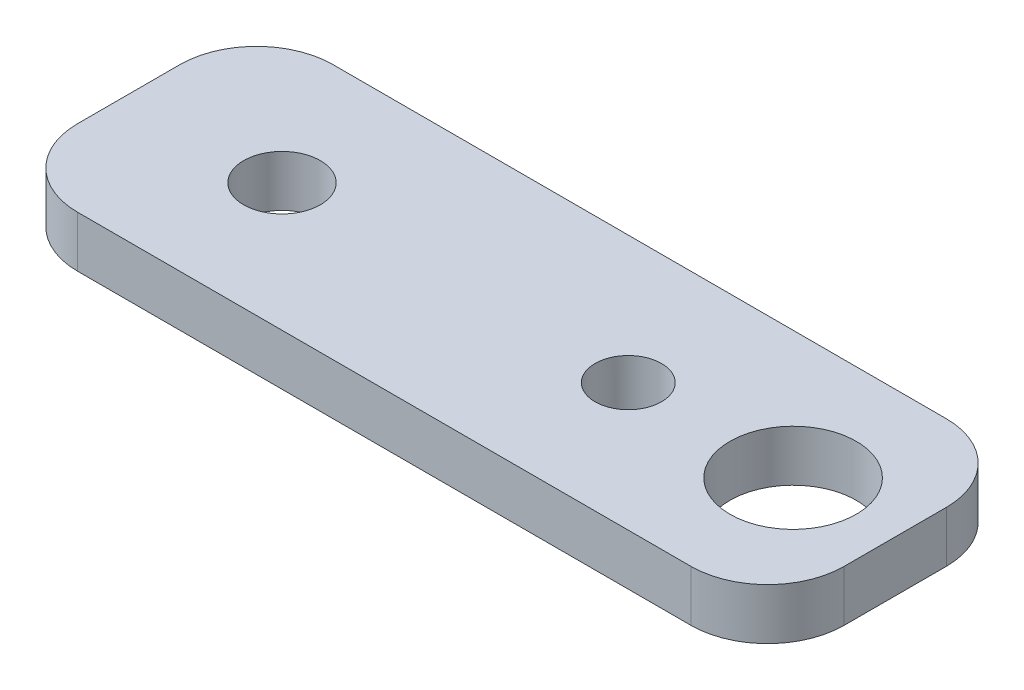
SolidWorks part; units mm, degrees
ref_plane "Front Plane" through (0, 0, 0) normal (0, 0, 1) x (1, 0, 0)
ref_plane "Top Plane" through (0, 0, 0) normal (0, 1, 0) x (1, 0, 0)
ref_plane "Right Plane" through (0, 0, 0) normal (1, 0, 0) x (0, 0, -1)
sketch "Sketch1" plane through (0, 0, 0) normal (0, 1, 0) x (1, 0, 0)
  line L1 (-15, 5) -> (15, 5)
  line L2 (-15, 5) -> (-15, -5)
  line L3 (-15, -5) -> (15, -5)
  line L4 (15, 5) -> (15, -5)
  line L5 (-15, 5) -> (15, -5) construction
  line L6 (-15, -5) -> (15, 5) construction
  point P0 (0, 0)
  dimension "D1" = 10
  dimension "D2" = 30
extrude "Boss-Extrude1" add sketch "Sketch1" along normal blind 2
sketch "Sketch2" plane through (0, 2, 0) normal (0, 1, 0) x (1, 0, 0)
  line L0 (11, 5) -> (11, -5) construction
  line L1 (-15, -5) -> (15, -5) construction
  line L2 (15, -5) -> (15, 5) construction
  circle A0 centre (11, 0) radius 2.4729
  circle A3 centre (4.55, 0) radius 1.3
  point P4 (15.0307, 0)
  point P5 (4.6832, 0)
  point P10 (11, 0)
  dimension "D1" = 6.45
  dimension "D2" = 4
extrude "Cut-Extrude1" cut sketch "Sketch2" against normal blind 3
fillet "Fillet1" radius 3 4 edges at (15, 1, 5) (15, 1, -5) (-15, 1, -5) (-15, 1, 5)
hole_wizard "Ø3.0 (3) Diameter Hole1" positions "Sketch3" profile "Sketch4" hole size "Ø3.0" standard "BSI" end condition through all
sketch "Sketch3" plane through (0, 2, 0) normal (0, 1, 0) x (1, 0, 0)
  circle A0 centre (11, 0) radius 2.4729 construction
  point P0 (-9, 0)
  dimension "D1" = 20
sketch "Sketch4" plane through (-9, 2, 0) normal (1, 0, 0) x (0, 0, 1)
  line L0 (0, 0) -> (0, 2)
  line L1 (0, 2) -> (1.5, 2)
  line L2 (1.5, 2) -> (1.5, 0)
  line L5 (1.5, 0) -> (0, 0)
  line L11 (0, -6.35) -> (0, 107.95) construction
  dimension "Thru Hole Dia." = 3
  dimension "Thru Hole Depth" = 2
